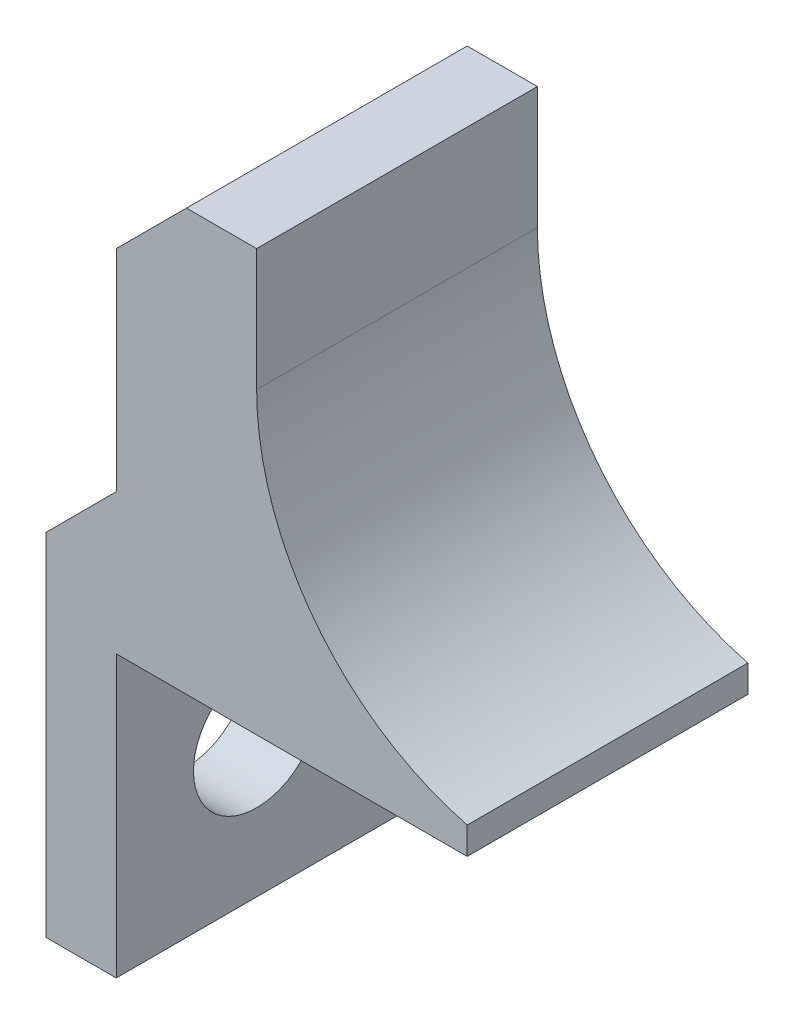
SolidWorks part; units mm, degrees
ref_plane "前视基准面" through (0, 0, 0) normal (0, 0, 1) x (1, 0, 0)
ref_plane "上视基准面" through (0, 0, 0) normal (0, 1, 0) x (1, 0, 0)
ref_plane "右视基准面" through (0, 0, 0) normal (1, 0, 0) x (0, 0, -1)
sketch "草图1" plane through (0, 0, 0) normal (0, 0, 1) x (1, 0, 0)
  line L0 (0, 0) -> (25, 0) construction
  line L1 (0, 5) -> (0, 30)
  line L3 (0, 0) -> (6.25, 0) construction
  line L4 (6.25, 0) -> (6.25, 21.3) construction
  line L5 (6.25, 21.3) -> (10, 21.3) construction
  line L6 (6.25, 0) -> (25, 0)
  line L7 (0, 30) -> (10, 30)
  line L8 (10, 30) -> (10, 21.3)
  line L9 (0, 0) -> (6.25, 0)
  line L14 (-5, 5) -> (0, 5)
  line L15 (0, 0) -> (0, -20)
  line L16 (0, -20) -> (-5, -20)
  line L17 (-5, -20) -> (-5, 5)
  line L19 (25, 0) -> (25, 1.9351)
  arc A2 (10, 21.3) -> (25, 1.9351) centre (30, 21.3) ccw
  dimension "D1" = 5
  dimension "D2" = 30
  dimension "D3" = 20
  dimension "D5" = 21.3
  dimension "D4" = 6.25
  dimension "D6" = 25
  dimension "D7" = 5
  dimension "D8" = 25
  dimension "D9" = 10
extrude "凸台-拉伸1" add sketch "草图1" along normal blind 20
sketch "草图3" plane through (-5, 0, 0) normal (-1, 0, 0) x (0, 0, 1)
  line L0 (0, -20) -> (10, -20) construction
  line L1 (20, -20) -> (0, -20) construction
  line L2 (10, -20) -> (10, -10) construction
  circle A0 centre (10, -10) radius 4.5
extrude "切除-拉伸2" cut sketch "草图3" against normal blind 20
chamfer "倒角1" distance 5 angle 45 1 edges at (0, 5, 10)
chamfer "倒角2" distance 5 angle 45 1 edges at (0, 30, 10)
